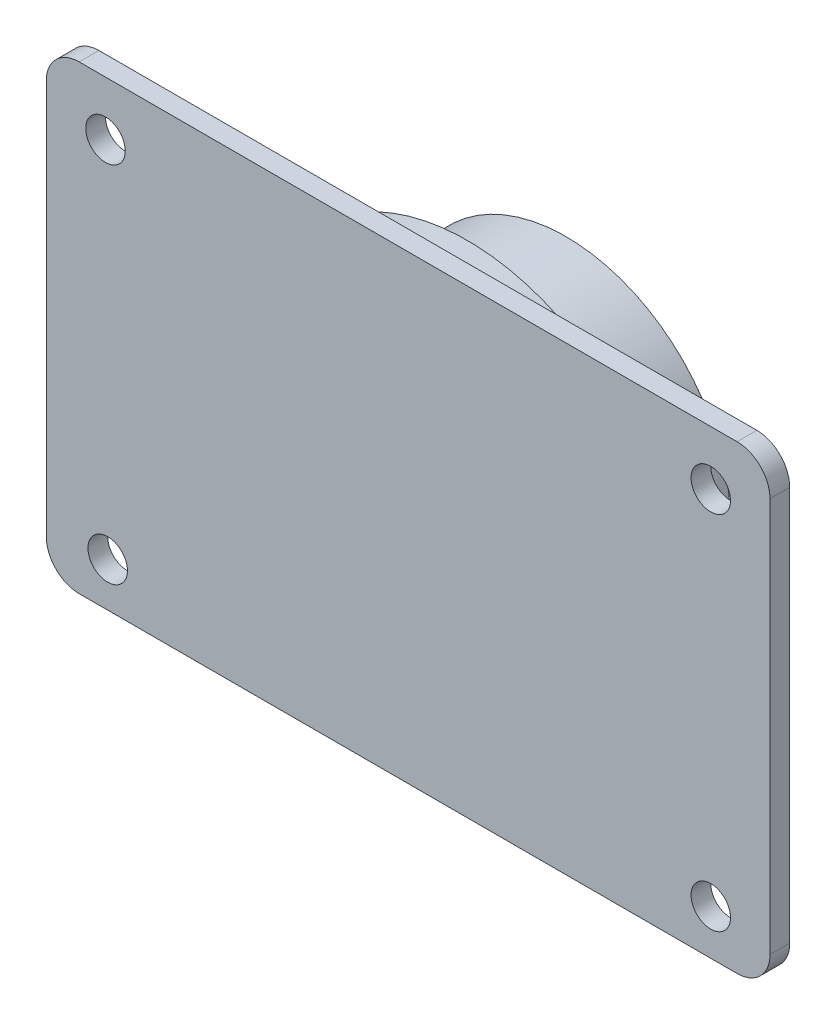
SolidWorks part; units mm, degrees
material "Cast Stainless Steel"
ref_plane "Front Plane" through (0, 0, 0) normal (0, 0, 1) x (1, 0, 0)
ref_plane "Top Plane" through (0, 0, 0) normal (0, 1, 0) x (1, 0, 0)
ref_plane "Right Plane" through (0, 0, 0) normal (1, 0, 0) x (0, 0, -1)
other "Center of Mass"
sketch "Sketch3" plane through (0, 0, 0) normal (0, 1, 0) x (1, 0, 0)
  circle A0 centre (0, 0) radius 25
extrude "Boss-Extrude1" add sketch "Sketch3" against normal blind 15 contours A0
sketch "Sketch4" plane through (0, -15, 0) normal (0, -1, 0) x (1, 0, 0)
  circle A0 centre (0, 0) radius 32
extrude "Boss-Extrude2" add sketch "Sketch4" along normal blind 6
sketch "Sketch6" plane through (0, -21, 0) normal (0, -1, 0) x (1, 0, 0)
  line L1 (35, 0) -> (35, -55)
  line L2 (35, -55) -> (-35, -55)
  line L3 (-35, -55) -> (-35, 55)
  line L4 (-35, 55) -> (35, 55)
  line L5 (35, 55) -> (35, 0)
extrude "Boss-Extrude3" add sketch "Sketch6" along normal blind 3
fillet "Fillet1" radius 5 1 edges at (35, -22.5, 55)
fillet "Fillet2" radius 5 3 edges at (-35, -22.5, 55) (-35, -22.5, -55) (35, -22.5, -55)
sketch "Sketch8" plane through (0, -24, 0) normal (0, -1, 0) x (1, 0, 0)
  circle A0 centre (26.7585, -46) radius 3
  circle A1 centre (-28.159, -46) radius 3
  circle A2 centre (26.7585, 46) radius 3
  circle A3 centre (-28.3209, 45.6631) radius 3
extrude "Cut-Extrude1" cut sketch "Sketch8" against normal blind 3 contours A3 | A2 | A1 | A0
ref_axis "Axis1" through (0, -15, 0) along (0, 1, 0)
ref_point "Point1"
move or copy body "Body-Move/Copy1" bodies to move or copy 106 copy no rotation origin (0, 0, 0) rotation axis (-0.5774, -0.5774, 0.5774) rotation angle 120
ref_axis "Axis2" through (0, 0, 15) along (0, 0, -1)
ref_point "Point2"
move or copy body "Body-Move/Copy2" bodies to move or copy 107 copy no translate (0, 0, -24)
